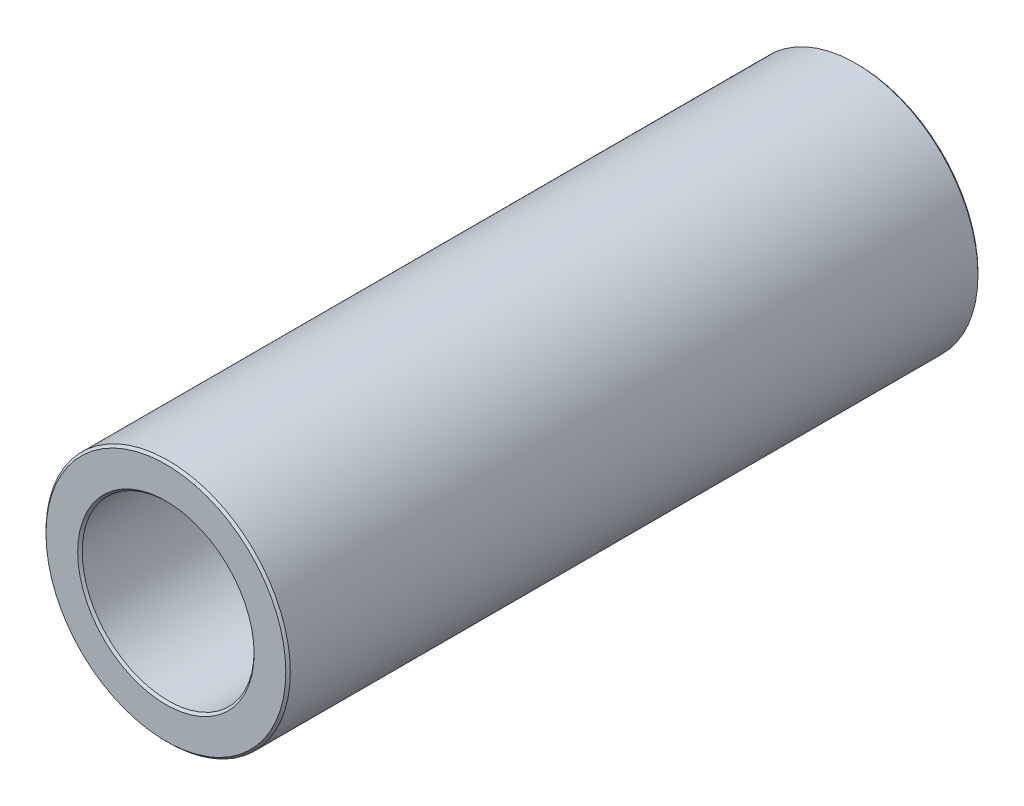
SolidWorks part; units mm, degrees
material "1.0037 (S235JR)"
ref_plane "E_Rechts" through (0, 0, 0) normal (0, 0, 1) x (1, 0, 0)
ref_plane "E_Oben" through (0, 0, 0) normal (0, 1, 0) x (1, 0, 0)
ref_plane "E_Vorne" through (0, 0, 0) normal (1, 0, 0) x (0, 0, -1)
ref_axis "A_Drehachse" through (0, 0, 55) along (0, 0, -1)
sketch "Skizze1" plane through (0, 0, 0) normal (0, 0, 1) x (1, 0, 0)
  circle A0 centre (0, 0) radius 27
  circle A1 centre (0, 0) radius 19
  dimension "D1" = 54
  dimension "D2" = 38
extrude "Aufsatz-Linear austragen1" add sketch "Skizze1" along normal mid plane 153
chamfer "Fase1" distance 0.5 angle 45 4 edges at (27, 0, -76.5) (27, 0, 76.5) (19, 0, -76.5) (19, 0, 76.5)
